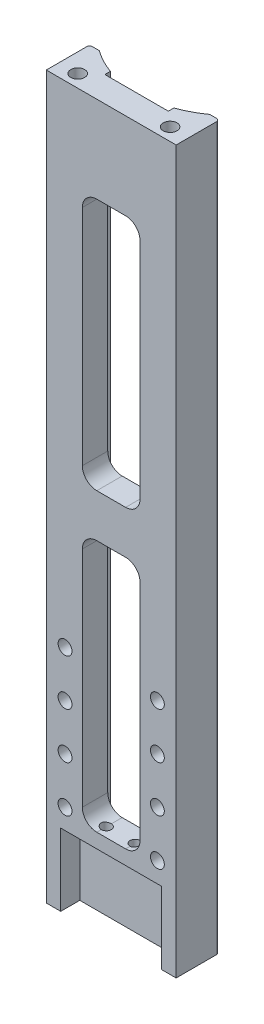
SolidWorks part; units mm, degrees
ref_plane "Ebene vorne" through (0, 0, 0) normal (0, 0, 1) x (1, 0, 0)
ref_plane "Ebene oben" through (0, 0, 0) normal (0, 1, 0) x (1, 0, 0)
ref_plane "Ebene rechts" through (0, 0, 0) normal (1, 0, 0) x (0, 0, -1)
sketch "Skizze1" plane through (0, 0, 0) normal (0, 1, 0) x (1, 0, 0)
  line L0 (-32.248, 0) -> (72.9564, 0) construction
  line L1 (-22.5, 7.5) -> (22.5, 7.5)
  line L2 (-22.5, 7.5) -> (-22.5, -7.5)
  line L3 (-22.5, -7.5) -> (22.5, -7.5)
  line L4 (22.5, 7.5) -> (22.5, -7.5)
  line L5 (0, 40.3012) -> (0, -36.3862) construction
  circle A0 centre (0, 34) radius 32.7
  dimension "D3" = 65.4
  dimension "D1" = 45
  dimension "D2" = 15
  dimension "D4" = 34
extrude "Rundung" add sketch "Skizze1" along normal blind 250 contours A0 L1 L2 L3 L4 region at (0, 0, 1.574)
sketch "Skizze2" plane through (0, 250, 0) normal (0, 1, 0) x (1, 0, 0)
  line L0 (0, 0) -> (0, 7.7395) construction
  line L1 (-11, 4.5707) -> (11, 4.5707)
  line L2 (-11, 4.5707) -> (-11, 1.3)
  line L3 (-11, 1.3) -> (11, 1.3)
  line L4 (11, 4.5707) -> (11, 1.3)
  line L5 (0, 7.7395) -> (0, -13.5524) construction
  arc A0 (-19.1583, 7.5) -> (19.1583, 7.5) centre (0, 34) ccw construction
  point P7 (0, 1.3)
  dimension "D1" = 22
extrude "AussparungLauf" cut sketch "Skizze2" against normal through all
sketch "Skizze4" plane through (0, 0, -1.3) normal (0, 0, -1) x (-1, 0, 0)
  line L0 (0, 0) -> (0, 250) construction
  line L1 (11, 250) -> (-11, 250) construction
  line L2 (0, 125) -> (27.3493, 125) construction
  line L3 (27.3493, 125) -> (-32.6088, 125) construction
  line L4 (-10, 117.5) -> (10, 117.5)
  line L5 (-10, 220) -> (10, 220)
  line L6 (-10, 220) -> (-10, 132.5)
  line L7 (-10, 132.5) -> (10, 132.5)
  line L8 (10, 220) -> (10, 132.5)
  line L9 (10, 30) -> (10, 117.5)
  line L10 (-10, 30) -> (10, 30)
  line L11 (-10, 30) -> (-10, 117.5)
  dimension "D1" = 20
  dimension "D2" = 30
  dimension "D3" = 7.5
extrude "Schnitt-Linear austragen2" cut sketch "Skizze4" against normal through all
sketch "Skizze5" plane through (0, 0, 7.5) normal (0, 0, 1) x (1, 0, 0)
  line L0 (0, 0) -> (0, 19.9205) construction
  line L1 (-22.5, 0) -> (22.5, 0) construction
  line L2 (-8.4823, 40) -> (10.0951, 40) construction
  circle A0 centre (-16, 32) radius 2.4
  circle A1 centre (16, 32) radius 2.4
  circle A2 centre (16, 48) radius 2.4
  circle A3 centre (16, 64) radius 2.4
  circle A4 centre (16, 80) radius 2.4
  circle A5 centre (-16, 48) radius 2.4
  circle A6 centre (-16, 64) radius 2.4
  circle A7 centre (-16, 80) radius 2.4
  point P8 (-16, 48)
  dimension "D1" = 4.8
  dimension "D2" = 32
  dimension "D3" = 8
  dimension "D4" = 32
  dimension "D5" = 2
  dimension "D6" = 4
extrude "Schnitt-Linear austragen4" cut sketch "Skizze5" against normal blind 6.4
ref_plane "Ebene1" through (0, 0, 1.1) normal (0, 0, 1) x (1, 0, 0)
sketch "Skizze6" plane through (0, 0, 1.1) normal (0, 0, 1) x (1, 0, 0)
  line L0 (-13.6, 32) -> (-18.4, 32) construction
  line L1 (-16, 34.4) -> (-16, 29.6) construction
  circle A0 centre (-16, 32) radius 2.4 construction
  circle A1 centre (-16, 32) radius 2.4 construction
  circle A2 centre (-16, 32) radius 2.85
  circle A3 centre (16, 32) radius 2.85
  circle A4 centre (16, 48) radius 2.85
  circle A5 centre (16, 64) radius 2.85
  circle A6 centre (16, 80) radius 2.85
  circle A7 centre (-16, 48) radius 2.85
  circle A8 centre (-16, 64) radius 2.85
  circle A9 centre (-16, 80) radius 2.85
  dimension "D1" = 5.7
  dimension "D2" = 2
  dimension "D3" = 4
extrude "Schnitt-Linear austragen5" cut sketch "Skizze6" against normal blind 1
sketch "Skizze9" plane through (0, 0, 0) normal (0, -1, 0) x (1, 0, 0)
  line L0 (0, -9.8662) -> (0, 13.0702) construction
  line L1 (-22.5, 7.5) -> (22.5, 7.5) construction
  line L2 (-17.5, 7.5) -> (17.5, 7.5)
  line L3 (-17.5, 7.5) -> (-17.5, 0.8949)
  line L4 (-17.5, 0.8949) -> (17.5, 0.8949)
  line L5 (17.5, 7.5) -> (17.5, 0.8949)
  dimension "D1" = 35
  dimension "D2" = 6.6051
extrude "Schnitt-Linear austragen9" cut sketch "Skizze9" against normal blind 25 contours L3 L2 L5 L4
sketch "Skizze12" plane through (0, 25, 0) normal (0, -1, 0) x (1, 0, 0)
  line L0 (0, 0) -> (0, 12.7189) construction
  line L5 (-5, 4.1975) -> (5, 4.1975) construction
  line L6 (-17.5, 0.8949) -> (17.5, 0.8949) construction
  line L7 (-17.5, 7.5) -> (17.5, 7.5) construction
  circle A0 centre (-5, 4.1975) radius 1.75
  circle A1 centre (5, 4.1975) radius 1.75
  dimension "D1" = 3.5
  dimension "D2" = 10
extrude "Schnitt-Linear austragen10" cut sketch "Skizze12" against normal up to next
sketch "Skizze14" plane through (0, 250, 0) normal (0, 1, 0) x (1, 0, 0)
  line L0 (0, 1.3) -> (0, -7.5) construction
  line L1 (-11, 1.3) -> (11, 1.3) construction
  line L2 (-22.5, -7.5) -> (22.5, -7.5) construction
  line L3 (-16, -3.1) -> (10.4076, -3.1) construction
  circle A0 centre (-16, -3.1) radius 2.4
  circle A1 centre (16, -3.1) radius 2.4
  dimension "D1" = 4.8
  dimension "D2" = 32
extrude "Schnitt-Linear austragen11" cut sketch "Skizze14" against normal blind 6.4
ref_plane "Ebene3" through (0, 243.6, 0) normal (0, 1, 0) x (1, 0, 0)
sketch "Skizze15" plane through (0, 243.6, 0) normal (0, 1, 0) x (1, 0, 0)
  line L0 (-18.4, -3.1) -> (-13.6, -3.1) construction
  line L1 (0, 0) -> (0, 10.8826) construction
  circle A0 centre (-16, -3.1) radius 2.4 construction
  circle A1 centre (-16, -3.1) radius 2.4 construction
  circle A2 centre (-16, -3.1) radius 2.9
  circle A3 centre (16, -3.1) radius 2.9
  dimension "D1" = 5.8
extrude "Schnitt-Linear austragen12" cut sketch "Skizze15" against normal blind 1.2
fillet "Verrundung1" radius 5 8 edges at (-10, 220, 3.1) (10, 220, 3.1) (-10, 132.5, 3.1) (10, 117.5, 3.1) (-10, 117.5, 3.1) (-10, 30, 3.1) (10, 132.5, 3.1) (10, 30, 3.1)
fillet "Verrundung2" radius 1 2 edges at (-22.5, 125, -7.5) (22.5, 125, -7.5)
